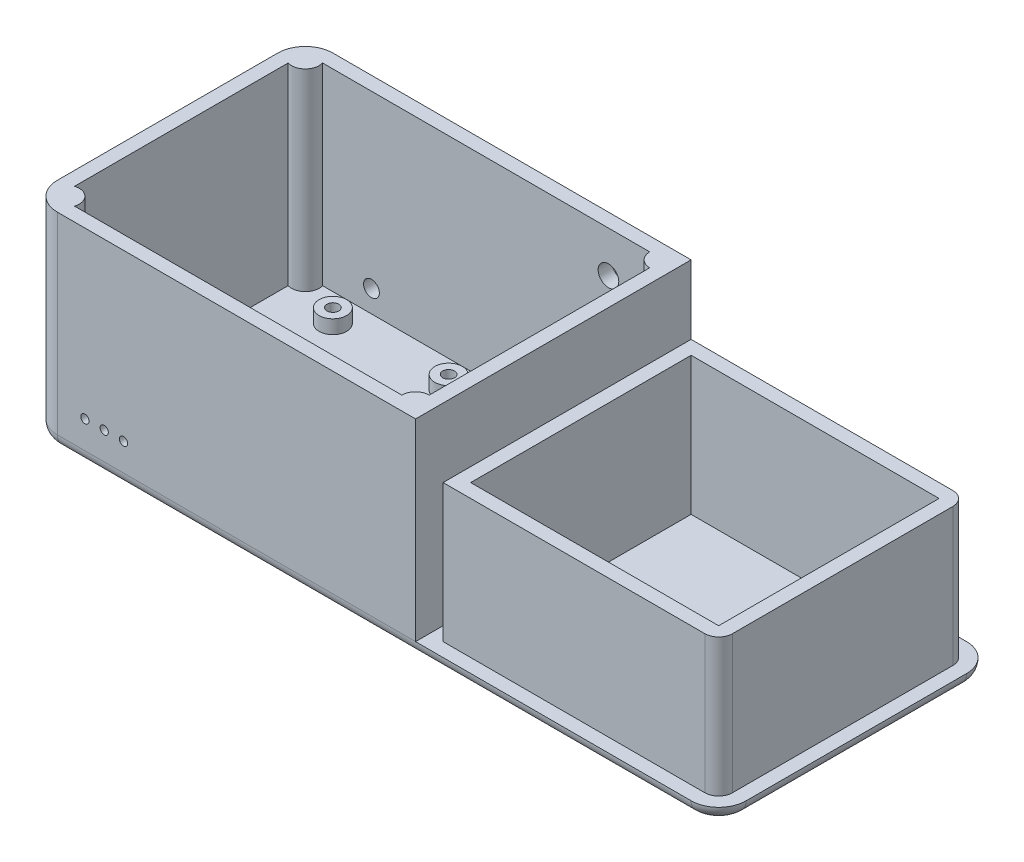
SolidWorks part; units mm, degrees
material "Custom Plastic"
ref_plane "Front Plane" through (0, 0, 0) normal (0, 0, 1) x (1, 0, 0)
ref_plane "Top Plane" through (0, 0, 0) normal (0, 1, 0) x (1, 0, 0)
ref_plane "Right Plane" through (0, 0, 0) normal (1, 0, 0) x (0, 0, -1)
sketch "Sketch1" plane through (0, 0, 0) normal (0, 1, 0) x (1, 0, 0)
  line L1 (-115, -50) -> (115, -50)
  line L2 (-125, -40) -> (-125, 40)
  line L3 (-115, 50) -> (115, 50)
  line L4 (125, -40) -> (125, 40)
  line L5 (-125, -50) -> (125, 50) construction
  line L6 (-125, 50) -> (125, -50) construction
  arc A0 (-115, -50) -> (-125, -40) centre (-115, -40) cw
  arc A1 (115, -50) -> (125, -40) centre (115, -40) ccw
  arc A2 (115, 50) -> (125, 40) centre (115, 40) cw
  arc A3 (-125, 40) -> (-115, 50) centre (-115, 40) cw
  point P0 (0, 0)
  dimension "D3" = 10
  dimension "D1" = 250
  dimension "D2" = 100
extrude "Boss-Extrude1" add sketch "Sketch1" along normal blind 5
fillet "Fillet1" radius 5 8 edges at (0, 0, 50) (122.0711, 0, 47.0711) (125, 0, 0) (122.0711, 0, -47.0711) (0, 0, -50) (-122.0711, 0, -47.0711) (-125, 0, 0) (-122.0711, 0, 47.0711)
sketch "Sketch2" plane through (0, 5, 0) normal (0, 1, 0) x (1, 0, 0)
  line L0 (-115, -45) -> (115, -45)
  line L1 (120, -40) -> (120, 40)
  line L2 (115, 45) -> (-115, 45)
  line L3 (-120, 40) -> (-120, -40)
  line L4 (-115, -50) -> (115, -50)
  line L5 (-115, -50) -> (115, -50)
  line L6 (125, -40) -> (125, 40)
  line L7 (125, -40) -> (125, 40)
  line L12 (15, 50) -> (15, -50)
  line L13 (10, 50) -> (10, -50)
  line L14 (20, 45) -> (20, -45)
  line L15 (115, 40) -> (20, 40)
  line L16 (115, 50) -> (-115, 50)
  line L17 (115, 50) -> (-115, 50)
  line L18 (-125, 40) -> (-125, -40)
  line L19 (-125, 40) -> (-125, -40)
  line L20 (115, 40) -> (115, -40)
  line L21 (115, -40) -> (20, -40)
  line L22 (20, 40) -> (20, -40)
  line L23 (25, 45) -> (25, -45)
  arc A0 (115, -45) -> (120, -40) centre (115, -40) ccw
  arc A1 (120, 40) -> (115, 45) centre (115, 40) ccw
  arc A2 (-115, 45) -> (-120, 40) centre (-115, 40) ccw
  arc A3 (-120, -40) -> (-115, -45) centre (-115, -40) ccw
  arc A4 (-125, -40) -> (-115, -50) centre (-115, -40) ccw
  arc A5 (-125, -40) -> (-115, -50) centre (-115, -40) ccw
  arc A6 (115, -50) -> (125, -40) centre (115, -40) ccw
  arc A7 (115, -50) -> (125, -40) centre (115, -40) ccw
  arc A16 (125, 40) -> (115, 50) centre (115, 40) ccw
  arc A17 (125, 40) -> (115, 50) centre (115, 40) ccw
  arc A18 (-115, 50) -> (-125, 40) centre (-115, 40) ccw
  arc A19 (-115, 50) -> (-125, 40) centre (-115, 40) ccw
  arc M25 (-125, -40) -> (-115, -50) centre (-115, -40) ccw
  line M26 (-115, -50) -> (115, -50)
  line M30 (115, 50) -> (-115, 50)
  arc M31 (-115, 50) -> (-125, 40) centre (-115, 40) ccw
  line M32 (-125, 40) -> (-125, -40)
  dimension "D8" = 5
  dimension "D10" = 5
  dimension "D11" = 5
  dimension "D13" = 5
  dimension "D2" = 5
  dimension "D3" = 5
  dimension "D4" = 5
  dimension "D5" = 5
  dimension "D6" = 5
  dimension "D7" = 5
  dimension "D9" = 5
  dimension "D12" = 5
  dimension "D14" = 5
  dimension "D15" = 140
  dimension "D16" = 5
  dimension "D17" = 5
extrude "Boss-Extrude2" add sketch "Sketch2" along normal blind 70 contours L2 L13 L0 L12 | L0 L13 L5 L12 | A3 L3 A2 L2 L13 L0 M30 M31 M32 M25 M26 | L13 L2 L12 M30 region at (12.5, 5, 47.5) region at (12.5, 5, 0) region at (8.32, 5, 47.5) region at (12.5, 5, -47.5)
extrude "Boss-Extrude3" add sketch "Sketch2<3>" along normal blind 50 contours L23 L15 L14 L21 | L1 A1 L2 L23 L15 L20 L21 L0 A0 | L23 L2 L14 L15 | L23 L21 L14 L0 region at (22.5, 5, 42.5) region at (26.3086, 5, 42.5) region at (22.5, 5, 0) region at (22.5, 5, -42.5)
sketch "Sketch2<3>" plane through (0, 5, 0) normal (0, 1, 0) x (1, 0, 0) same geometry as "Sketch2"
sketch "Sketch3" plane through (0, 75, 0) normal (0, 1, 0) x (1, 0, 0)
  line L0 (15, 50) -> (15, -50) construction
  line L1 (15, 50) -> (15, -50) construction
  circle A0 centre (-118.5355, 43.5355) radius 5
  arc A1 (-115, 45) -> (-120, 40) centre (-115, 40) ccw construction
  circle A2 centre (10, 45) radius 5
  circle A3 centre (10, -45) radius 5
  circle A4 centre (-118.5355, -43.5355) radius 5
  arc A5 (-120, -40) -> (-115, -45) centre (-115, -40) ccw construction
  arc A6 (-125, -40) -> (-115, -50) centre (-115, -40) ccw construction
extrude "Boss-Extrude4" add sketch "Sketch3" against normal up to surface (70 mm away) up to face at (-75.3452, 5, 0)
sketch "Sketch4" plane through (10, 0, 0) normal (-1, 0, 0) x (0, 0, 1)
  line L0 (40, 5) -> (-40, 5) construction
  line L1 (3.75, 10) -> (-3.75, 10)
  line L2 (3.75, 10) -> (3.75, 5)
  line L3 (3.75, 5) -> (-3.75, 5)
  line L4 (-3.75, 10) -> (-3.75, 5)
  line L5 (3.75, 10) -> (-3.75, 5) construction
  line L6 (3.75, 5) -> (-3.75, 10) construction
  point P0 (0, 7.5)
  dimension "D1" = 5
  dimension "D2" = 7.5
extrude "Cut-Extrude1" cut sketch "Sketch4" against normal up to surface (15 mm away) up to face at (25, 30, 0)
sketch "Sketch5" plane through (0, 0, -45) normal (0, 0, 1) x (1, 0, 0)
  line L0 (5, 5) -> (-113.7548, 5) construction
  line L1 (-120, 75) -> (-120, 5) construction
  line L2 (5, 75) -> (-113.7548, 75) construction
  line L3 (5, 75) -> (5, 5) construction
  circle A0 centre (-96, 13) radius 2.875
  circle A1 centre (-10, 60) radius 3.75
  dimension "D1" = 5.75
  dimension "D4" = 7.5
  dimension "D2" = 8
  dimension "D3" = 24
  dimension "D5" = 15
  dimension "D6" = 15
extrude "Cut-Extrude2" cut sketch "Sketch5" against normal up to surface (5 mm away)
sketch "Sketch6" plane through (0, 0, 50) normal (0, 0, 1) x (1, 0, 0)
  line L0 (-115, 75) -> (-115, 5) construction
  line L1 (-115, 5) -> (15, 5) construction
  circle A0 centre (-105, 15) radius 1.5
  circle A1 centre (-98, 15) radius 1.5
  circle A2 centre (-91, 15) radius 1.5
  dimension "D1" = 3
  dimension "D5" = 7
  dimension "D2" = 10
  dimension "D3" = 10
  dimension "D4" = 3
extrude "Cut-Extrude3" cut sketch "Sketch6" against normal up to surface (5 mm away) up to face at (-54.3774, 40, 45)
sketch "Sketch8" plane through (0, 5, 0) normal (0, 1, 0) x (1, 0, 0)
  line L0 (-113.7548, -45) -> (5, -45) construction
  line L1 (-120, 38.7548) -> (-120, -38.7548) construction
  circle A0 centre (-100, -25) radius 5
  circle A1 centre (-58, -25) radius 5
  circle A2 centre (-58, 35) radius 5
  circle A3 centre (-100, 35) radius 5
  circle A4 centre (-100, -25) radius 2.15
  circle A5 centre (-58, -25) radius 2.15
  circle A6 centre (-58, 35) radius 2.15
  circle A7 centre (-100, 35) radius 2.15
  dimension "D1" = 10
  dimension "D4" = 20
  dimension "D5" = 60
  dimension "D6" = 42
  dimension "D7" = 20
  dimension "D8" = 4.3
  dimension "D2" = 2
  dimension "D3" = 2
extrude "Boss-Extrude5" add sketch "Sketch8" along normal blind 5
equation "\"device_length\"=250"
equation "\"D1@Sketch1\"=\"device_length\""
equation "\"device_width\" = 100"
equation "\"D2@Sketch1\"=\"device_width\""
equation "\"device_wall\"=5"
equation "\"D2@Sketch2\"=\"device_wall\""
equation "\"device_base\"= 5"
equation "\"D1@Boss-Extrude1\"=\"device_base\""
equation "\"D1@Fillet1\"=\"device_base\""
equation "\"D3@Sketch2\"=\"device_wall\""
equation "\"D4@Sketch2\"=\"device_wall\""
equation "\"D5@Sketch2\"=\"device_wall\""
equation "\"D6@Sketch2\"=\"device_wall\""
equation "\"D7@Sketch2\"=\"device_wall\""
equation "\"D8@Sketch2\"=\"device_wall\""
equation "\"D9@Sketch2\"=\"device_wall\""
equation "\"D10@Sketch2\"=\"device_wall\""
equation "\"D11@Sketch2\"=\"device_wall\""
equation "\"D12@Sketch2\"=\"device_wall\""
equation "\"D13@Sketch2\"=\"device_wall\""
equation "\"D14@Sketch2\"=\"device_wall\""
equation "\"main_length\"=140"
equation "\"D15@Sketch2\"=\"main_length\""
equation "\"device_height\"=75"
equation "\"D1@Boss-Extrude2\"=\"device_height\"-\"device_base\""
equation "\"D16@Sketch2\"=\"device_wall\""
equation "\"D17@Sketch2\"=\"device_wall\""
equation "\"inner_black_box\"=50"
equation "\"D1@Boss-Extrude3\"=\"inner_black_box\""
equation "\"D6@Sketch5\"=\"D5@Sketch5\""
